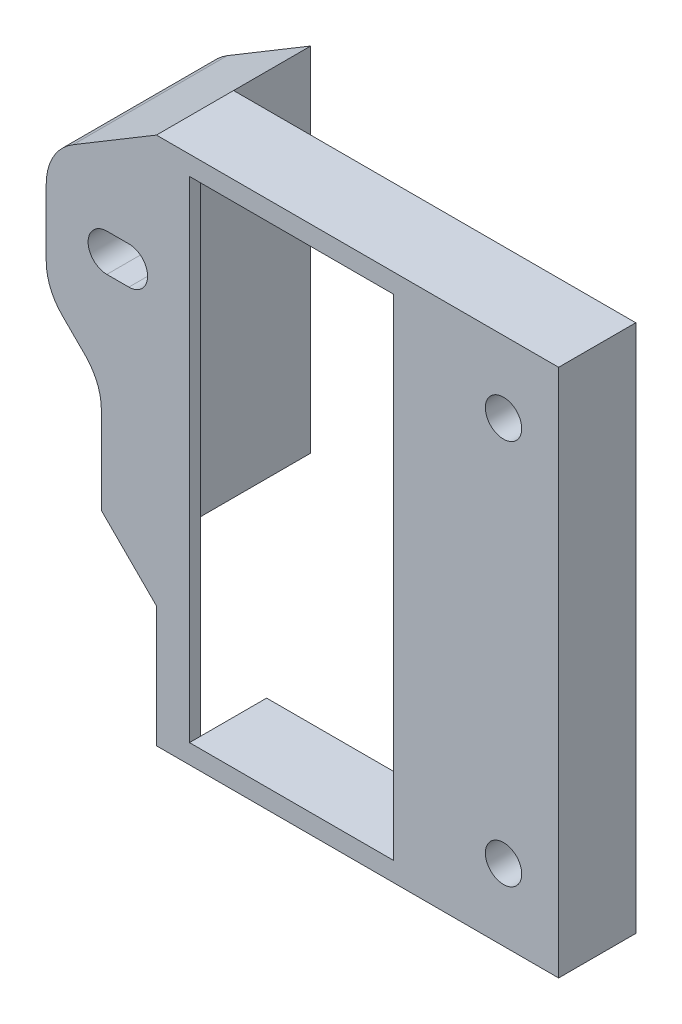
SolidWorks part; units mm, degrees
ref_plane "Plano frontal" through (0, 0, 0) normal (0, 0, 1) x (1, 0, 0)
ref_plane "Plano superior" through (0, 0, 0) normal (0, 1, 0) x (1, 0, 0)
ref_plane "Plano direito" through (0, 0, 0) normal (1, 0, 0) x (0, 0, -1)
sketch "Esboço1" plane through (0, 0, 0) normal (0, 0, 1) x (1, 0, 0)
  line L1 (-9.25, 22.25) -> (9.25, 22.25)
  line L2 (-9.25, 22.25) -> (-9.25, -22.25)
  line L3 (-9.25, -22.25) -> (9.25, -22.25)
  line L4 (9.25, 22.25) -> (9.25, -22.25)
  line L5 (-9.25, 22.25) -> (9.25, -22.25) construction
  line L6 (-9.25, -22.25) -> (9.25, 22.25) construction
  line L7 (-12.25, 24) -> (12.25, 24)
  line L8 (-12.25, 24) -> (-12.25, -24)
  line L9 (-12.25, -24) -> (12.25, -24)
  line L10 (12.25, 24) -> (12.25, -24)
  line L11 (-12.25, 24) -> (12.25, -24) construction
  line L12 (-12.25, -24) -> (12.25, 24) construction
  point P0 (0, 0)
  point P6 (0, 0)
  dimension "D1" = 44.5
  dimension "D2" = 18.5
  dimension "D3" = 3
  dimension "D4" = 48
extrude "Ressalto-extrusão1" add sketch "Esboço1" along normal blind 1
sketch "Esboço2" plane through (0, 0, 1) normal (0, 0, 1) x (1, 0, 0)
  line L1 (12.25, 24) -> (24.25, 24)
  line L2 (12.25, 22.25) -> (12.25, -22.25)
  line L3 (12.25, -24) -> (24.25, -24)
  line L4 (24.25, 24) -> (24.25, -24)
  line L7 (-12.25, 24) -> (12.25, 24)
  line L8 (9.25, -22.25) -> (9.25, 22.25) construction
  line L9 (-12.25, 22.25) -> (12.25, 22.25)
  line L10 (0, 0) -> (6.5568, 0) construction
  line L11 (-12.25, 24) -> (-12.25, -24) construction
  line L12 (9.25, 22.25) -> (-9.25, 22.25) construction
  line L13 (-12.25, 24) -> (-12.25, 22.25)
  line L14 (12.25, -22.25) -> (-9.25, -22.25)
  line L15 (-9.25, -22.25) -> (-9.25, -24)
  line L16 (-9.25, -24) -> (12.25, -24)
  line L17 (12.25, -24) -> (12.25, 24) construction
  line L18 (-9.25, -22.25) -> (9.25, -22.25) construction
  circle A0 centre (19.25, 17.5) radius 1.65
  circle A1 centre (19.25, -17.5) radius 1.65
  point P12 (11.25, 24)
  point P26 (-9.25, -22.25)
  point P27 (12.25, -22.8985)
  dimension "D4" = 3.3
  dimension "D1" = 13
  dimension "D2" = 2
  dimension "D3" = 8
  dimension "D5" = 35
extrude "Ressalto-extrusão2" add sketch "Esboço2" against normal blind 7
sketch "Esboço4" plane through (0, 0, 1) normal (0, 0, 1) x (1, 0, 0)
  line L0 (-12.25, 24) -> (-22.25, 18)
  line L1 (-22.25, 18) -> (-22.25, 7)
  line L2 (-22.25, 7) -> (-17.25, 2)
  line L3 (-17.25, 2) -> (-17.25, -8)
  line L4 (-27.7955, -3) -> (-12.25, -3) construction
  line L5 (-22.25, -24) -> (-12.25, -24)
  line L6 (-12.25, -24) -> (-12.25, 24)
  line L7 (-22.25, -13) -> (-17.25, -8)
  line L8 (-22.25, -24) -> (-22.25, -13)
  line L10 (-16.75, 12.5) -> (-14.75, 12.5) construction
  line L11 (-16.75, 14.2) -> (-14.75, 14.2)
  line L12 (-16.75, 10.8) -> (-14.75, 10.8)
  line L13 (-16.75, -18.5) -> (-14.75, -18.5) construction
  line L14 (-16.75, -20.2) -> (-14.75, -20.2)
  line L15 (-16.75, -16.8) -> (-14.75, -16.8)
  line L17 (-22.25, -13) -> (-9.25, -13) construction
  line L18 (-9.25, 22.25) -> (-9.25, -22.25) construction
  line L19 (-17.25, -8) -> (-12.25, -8)
  arc A0 (-16.75, 14.2) -> (-16.75, 10.8) centre (-16.75, 12.5) ccw
  arc A1 (-14.75, 10.8) -> (-14.75, 14.2) centre (-14.75, 12.5) ccw
  arc A2 (-16.75, -20.2) -> (-16.75, -16.8) centre (-16.75, -18.5) cw
  arc A3 (-14.75, -16.8) -> (-14.75, -20.2) centre (-14.75, -18.5) cw
  circle A5 centre (19.25, -17.5) radius 1.65 construction
  point P13 (-15.75, 12.5)
  point P20 (-15.75, -18.5)
  point P26 (-15.75, -13)
  point P32 (-22.25, -18.5)
  line M24 (-12.25, 24) -> (-12.25, -24)
  dimension "D7" = 1.7
  dimension "D2" = 45
  dimension "D3" = 18.5
  dimension "D5" = 5
  dimension "D6" = 2
  dimension "D8" = 31
  dimension "D9" = 34
extrude "Ressalto-extrusão3" add sketch "Esboço4" against normal blind 14 contours L3 L19 L0 L1 L2 A1 L12 A0 L11 M24 region at (-16.3387, 8.5326, 1)
fillet "Filete1" radius 5 3 edges at (-17.25, 2, -6) (-22.25, 18, -6) (-22.25, 7, -6)
chamfer "Chanfro4" distance 5 angle 45 1 edges at (-12.25, -8, 0.5)
